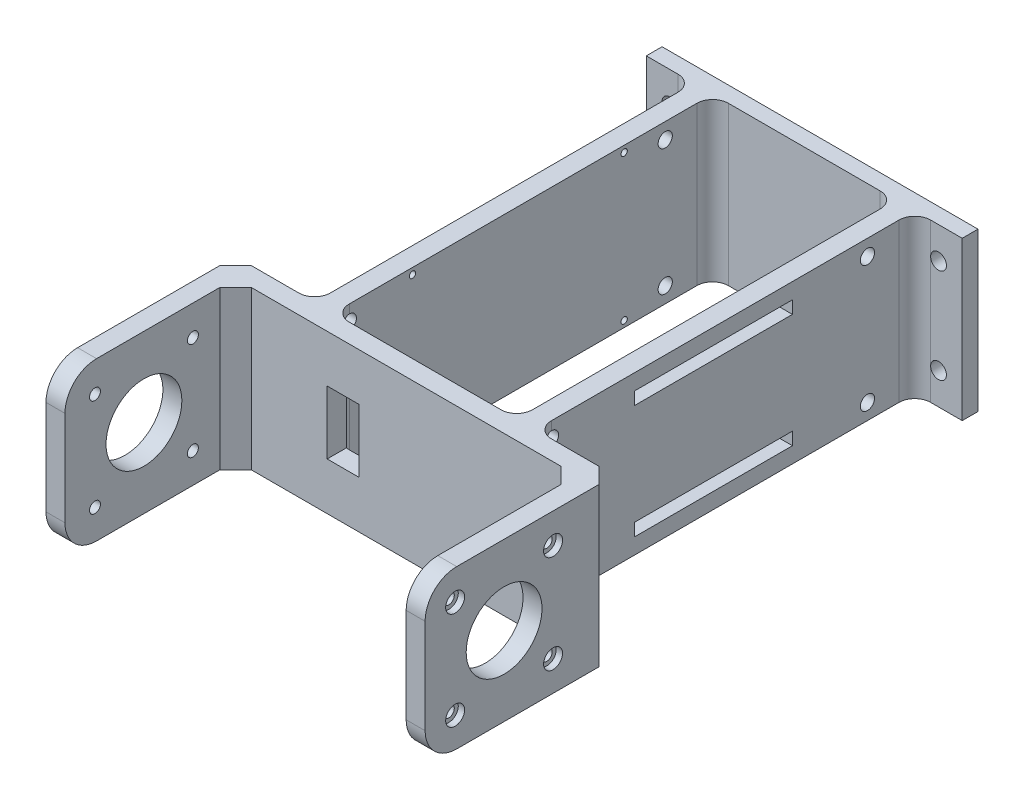
SolidWorks part; units mm, degrees
ref_plane "Front Plane" through (0, 0, 0) normal (0, 0, 1) x (1, 0, 0)
ref_plane "Top Plane" through (0, 0, 0) normal (0, 1, 0) x (1, 0, 0)
ref_plane "Right Plane" through (0, 0, 0) normal (1, 0, 0) x (0, 0, -1)
sketch "Sketch1" plane through (0, 0, 0) normal (0, 1, 0) x (1, 0, 0)
  line L1 (-60, 35) -> (60, 35)
  line L2 (-60, 35) -> (-60, -30)
  line L3 (-60, -30) -> (60, -30)
  line L4 (60, 35) -> (60, -30)
  line L5 (-54, 29) -> (54, 29)
  line L6 (-54, 29) -> (-54, -25)
  line L7 (-54, -25) -> (54, -25)
  line L8 (54, 29) -> (54, -25)
  dimension "D1" = 120
  dimension "D2" = 6
  dimension "D3" = 6
  dimension "D4" = 6
  dimension "D5" = 5
  dimension "D6" = 65
extrude "Boss-Extrude1" add sketch "Sketch1" along normal blind 50
sketch "Sketch4" plane through (-60, 0, 0) normal (-1, 0, 0) x (0, 0, 1)
  line L0 (-35, 50) -> (-35, 0) construction
  circle A0 centre (0, 25) radius 12
  point P4 (-35, 25)
  dimension "D1" = 24
  dimension "D2" = 35
extrude "Cut-Extrude1" cut sketch "Sketch4" against normal blind 156
sketch "Sketch7" plane through (-60, 0, 0) normal (-1, 0, 0) x (0, 0, 1)
  circle A0 centre (-15.5, 9.5) radius 1.7353
  circle A1 centre (-15.5, 40.5) radius 1.7353
  circle A2 centre (15.5, 9.5) radius 1.7353
  circle A3 centre (15.5, 40.5) radius 1.7353
  circle A4 centre (0, 25) radius 12 construction
  dimension "D1" = 31
  dimension "D2" = 31
  dimension "D3" = 15.5
  dimension "D4" = 15.5
extrude "Cut-Extrude2" cut sketch "Sketch7" against normal blind 156
sketch "Sketch9" plane through (60, 0, 0) normal (1, 0, 0) x (0, 0, -1)
  circle A0 centre (15.5, 40.5) radius 3
  circle A1 centre (15.5, 9.5) radius 3
  circle A2 centre (-15.5, 9.5) radius 3
  circle A3 centre (-15.5, 40.5) radius 3
extrude "Cut-Extrude3" cut sketch "Sketch9" against normal blind 2
sketch "Sketch10" plane through (-60, 0, 0) normal (-1, 0, 0) x (0, 0, 1)
  circle A0 centre (-15.5, 9.5) radius 3
  circle A1 centre (-15.5, 40.5) radius 3
  circle A2 centre (15.5, 40.5) radius 3
  circle A3 centre (15.5, 9.5) radius 3
extrude "Cut-Extrude4" cut sketch "Sketch10" against normal blind 2
sketch "Sketch11" plane through (0, 0, -35) normal (0, 0, -1) x (-1, 0, 0)
  line L0 (-60, 50) -> (60, 50) construction
  line L1 (-35, 50) -> (35, 50)
  line L2 (-35, 50) -> (-35, 0)
  line L3 (-35, 0) -> (35, 0)
  line L4 (35, 50) -> (35, 0)
  line L5 (-60, 0) -> (60, 0) construction
  line L6 (-29, 50) -> (29, 50)
  line L7 (-29, 50) -> (-29, 0)
  line L8 (-29, 0) -> (29, 0)
  line L9 (29, 50) -> (29, 0)
  line L10 (-60, 50) -> (-60, 0) construction
  line L11 (60, 50) -> (60, 0) construction
  line M3 (60, 50) -> (-60, 50)
  dimension "D1" = 25
  dimension "D2" = 25
  dimension "D3" = 6
  dimension "D4" = 6
extrude "Boss-Extrude2" add sketch "Sketch11" along normal blind 120 contours L7 L2 L3 M3 | L9 L3 L4 M3 region at (32, 25, -35) region at (-32, 25, -35)
sketch "Sketch13" plane through (0, 50, 0) normal (0, 1, 0) x (1, 0, 0)
  line L0 (-60, 35) -> (-60, -30) construction
  line L1 (-60, -25) -> (60, -25)
  line L2 (-60, -25) -> (-60, -30)
  line L3 (-60, -30) -> (60, -30)
  line L4 (60, -25) -> (60, -30)
  line L5 (-54, -25) -> (54, -25) construction
extrude "Cut-Extrude5" cut sketch "Sketch13" against normal blind 120
fillet "Fillet1" radius 10 4 edges at (57, 0, 25) (-57, 0, 25) (57, 50, 25) (-57, 50, 25)
sketch "Sketch14" plane through (0, 0, -155) normal (0, 0, -1) x (-1, 0, 0)
  line L0 (-60, 50) -> (-60, 0) construction
  line L1 (50, 0) -> (-50, 0)
  line L2 (50, 0) -> (50, 50)
  line L3 (50, 50) -> (-50, 50)
  line L4 (-50, 0) -> (-50, 50)
  line L5 (35, 50) -> (60, 50) construction
  dimension "D1" = 100
  dimension "D2" = 50
  dimension "D3" = 10
extrude "Boss-Extrude3" add sketch "Sketch14" along normal blind 5
sketch "Sketch15" plane through (0, 0, -160) normal (0, 0, -1) x (-1, 0, 0)
  line L0 (-50, 0) -> (50, 0) construction
  line L1 (50, 50) -> (-50, 50) construction
  line L2 (-50, 50) -> (-50, 0) construction
  line L3 (50, 0) -> (50, 50) construction
  circle A0 centre (-42.5, 10) radius 2.5
  circle A1 centre (42.5, 10) radius 2.5
  circle A2 centre (42.5, 40) radius 2.5
  circle A3 centre (-42.5, 40) radius 2.5
  dimension "D1" = 5
  dimension "D2" = 10
  dimension "D3" = 10
  dimension "D4" = 7.5
  dimension "D5" = 7.5
extrude "Cut-Extrude6" cut sketch "Sketch15" against normal blind 18
sketch "Sketch16" plane through (35, 0, 0) normal (1, 0, 0) x (0, 0, -1)
  line L1 (66.2618, 45) -> (116.2618, 45)
  line L2 (66.2618, 45) -> (66.2618, 41)
  line L3 (66.2618, 41) -> (116.2618, 41)
  line L4 (116.2618, 45) -> (116.2618, 41)
  line L5 (66.2618, 9) -> (116.2618, 9)
  line L6 (66.2618, 9) -> (66.2618, 5)
  line L7 (66.2618, 5) -> (116.2618, 5)
  line L8 (116.2618, 9) -> (116.2618, 5)
extrude "Cut-Extrude7" cut sketch "Sketch16" against normal blind 18
sketch "Sketch17" plane through (-35, 0, 0) normal (-1, 0, 0) x (0, 0, 1)
  line L0 (-35, 50) -> (-35, 0) construction
  line L1 (-155, 0) -> (-35, 0) construction
  circle A0 centre (-127, 2) radius 1
  circle A1 centre (-127, 48) radius 1
  circle A2 centre (-60, 2) radius 1
  circle A3 centre (-60, 48) radius 1
  dimension "D1" = 46
  dimension "D4" = 2
  dimension "D2" = 67
  dimension "D3" = 25
  dimension "D5" = 2
extrude "Cut-Extrude8" cut sketch "Sketch17" against normal blind 18
sketch "Sketch18" plane through (0, 0, -35) normal (0, 0, -1) x (-1, 0, 0)
  line L1 (25, 35) -> (15, 35)
  line L2 (25, 35) -> (25, 15)
  line L3 (25, 15) -> (15, 15)
  line L4 (15, 35) -> (15, 15)
extrude "Cut-Extrude9" cut sketch "Sketch18" against normal blind 18
sketch "Sketch22" plane through (-35, 0, 0) normal (-1, 0, 0) x (0, 0, 1)
  line L0 (-155, 50) -> (-35, 50) construction
  line L1 (-155, 0) -> (-35, 0) construction
  line L2 (-35, 50) -> (-35, 0) construction
  line L3 (-35, 50) -> (-35, 0) construction
  circle A0 centre (-140, 5) radius 2.25
  circle A1 centre (-140, 45) radius 2.25
  circle A2 centre (-40, 5) radius 2.25
  circle A3 centre (-40, 45) radius 2.25
  dimension "D1" = 5
  dimension "D3" = 5
  dimension "D6" = 4.5
  dimension "D2" = 5
  dimension "D4" = 5
  dimension "D5" = 100
extrude "Cut-Extrude13" cut sketch "Sketch22" against normal blind 75
chamfer "Chamfer1" distance 5 angle 45 2 edges at (-60, 25, -35) (60, 25, -35)
chamfer "Chamfer2" distance 5 angle 45 2 edges at (54, 25, -29) (-54, 25, -29)
fillet "Fillet2" radius 5 8 edges at (-29, 25, -155) (29, 25, -155) (-29, 25, -35) (-35, 25, -35) (-35, 25, -155) (35, 25, -155)
